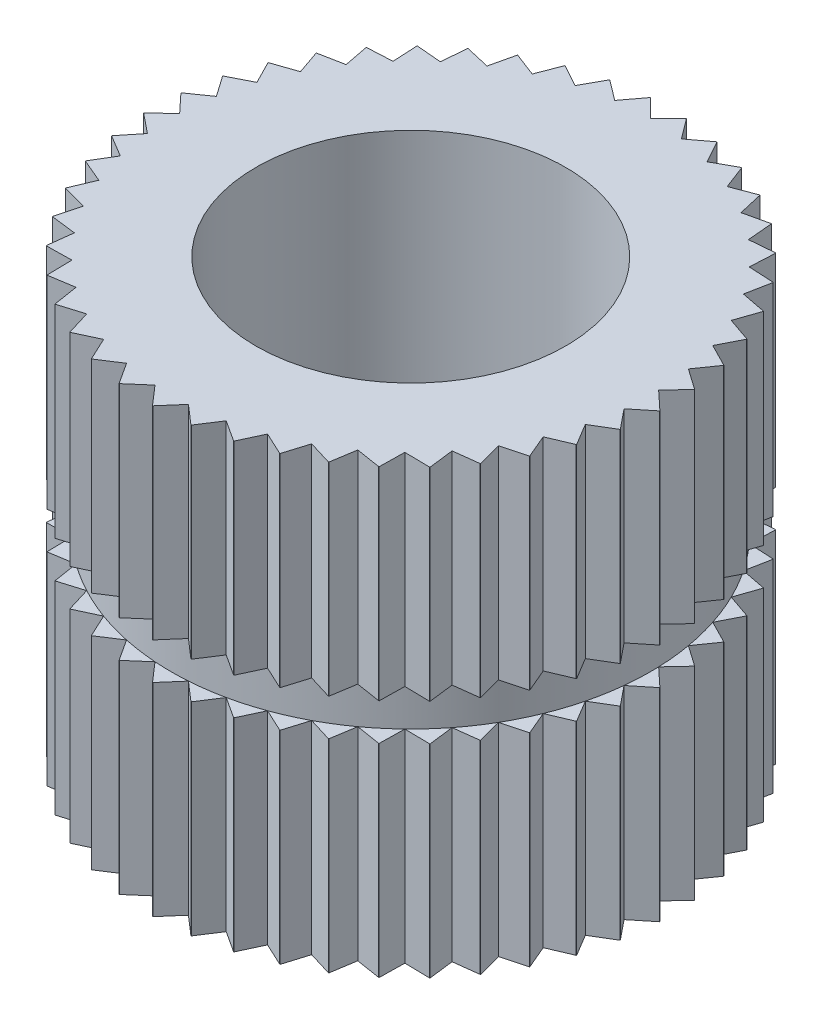
SolidWorks part; units mm, degrees
material "Brass"
ref_plane "Front Plane" through (0, 0, 0) normal (0, 0, 1) x (1, 0, 0)
ref_plane "Top Plane" through (0, 0, 0) normal (0, 1, 0) x (1, 0, 0)
ref_plane "Right Plane" through (0, 0, 0) normal (1, 0, 0) x (0, 0, -1)
sketch "Sketch1" plane through (0, 0, 0) normal (0, 0, 1) x (1, 0, 0)
  line L0 (0, 0) -> (0, 14.9316) construction
  line L1 (0, 0) -> (0, 6)
  line L2 (0, 6) -> (-3.5, 6)
  line L3 (-3.5, 6) -> (-3.5, 3.25)
  line L4 (-3.5, 3.25) -> (-3.25, 3.25)
  line L5 (-3.25, 3.25) -> (-3.25, 2.75)
  line L6 (-3.25, 2.75) -> (-3.5, 2.75)
  line L7 (-3.5, 2.75) -> (-3.5, 0)
  line L8 (-3.5, 0) -> (0, 0)
  dimension "D1" = 7
  dimension "D2" = 6
  dimension "D3" = 2.75
  dimension "D4" = 2.75
  dimension "D5" = 0.25
revolve "Revolve1" add sketch "Sketch1" angle 360 about L0
sketch "Sketch2" plane through (0, 6, 0) normal (0, 1, 0) x (1, 0, 0)
  line L0 (0, 3.25) -> (0.2416, 3.4916)
  line L1 (0, 3.25) -> (-0.2416, 3.4916)
  circle A0 centre (0, 0) radius 3.5
  circle A1 centre (0, 0) radius 3.25
  dimension "D1" = 0.25
  dimension "D2" = 7
extrude "Cut-Extrude1" cut sketch "Sketch2" against normal through all contours L1 L0 region at (0, 6, -3.4148)
ref_axis "Axis1" through (0, 6.3, 0) along (0, -1, 0)
pattern_circular "CirPattern1" count 45 over 360 about axis through (0, 6.3, 0) along (0, -1, 0) of "Cut-Extrude1"
hole_wizard "M5x0.8 Tapped Hole1" positions "Sketch3" profile "Sketch4" tap size "M5x0.8" standard "ANSI Metric" end condition through all
sketch "Sketch3" plane through (0, 6, 0) normal (0, 1, 0) x (1, 0, 0)
  point P0 (0, 0)
sketch "Sketch4" plane through (0, 6, 0) normal (1, 0, 0) x (0, 0, 1)
  line L0 (0, 0) -> (0, 6)
  line L1 (0, 6) -> (2.1, 6)
  line L2 (2.1, 6) -> (2.1, 0)
  line L5 (2.1, 0) -> (0, 0)
  line L11 (0, -6.35) -> (0, 107.95) construction
  dimension "Thru Tap Drill Dia." = 4.2
  dimension "Thru Tap Drill Depth" = 6
cosmetic thread "Hole Thread1" parameters "D2"=5
